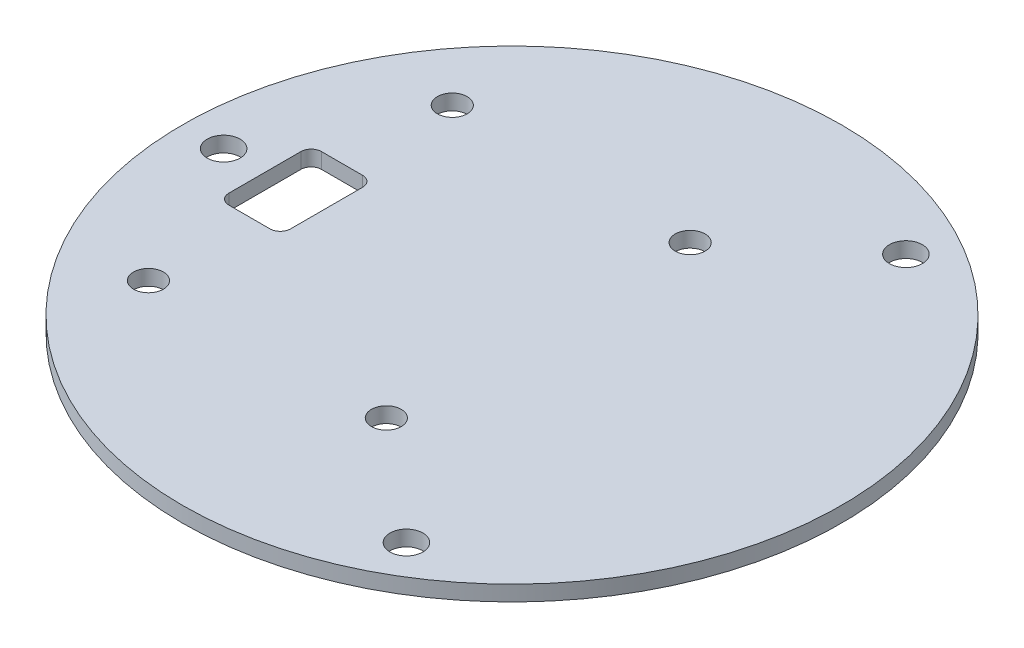
SolidWorks part; units mm, degrees
note: The reader was unsure of these and kept them because the rebuilt part matched: thickness of "Base-Flange1", "Sheet-Metal1", "Sheet-Metal2", "Sheet-Metal4", "Sheet-Metal5".
ref_plane "Front Plane" through (0, 0, 0) normal (0, 0, 1) x (1, 0, 0)
ref_plane "Top Plane" through (0, 0, 0) normal (0, 1, 0) x (1, 0, 0)
ref_plane "Right Plane" through (0, 0, 0) normal (1, 0, 0) x (0, 0, -1)
sketch "Sketch1" plane through (0, 0, 0) normal (0, 1, 0) x (1, 0, 0)
  circle A1 centre (0, 0) radius 32
  dimension "D2" = 64
base flange "Base-Flange1" sketch "Sketch1" thickness 1.5 reverse thickness direction no parameters "D1"=1.5
sketch "Sketch6" plane through (0, 0, 0) normal (0, 1, 0) x (1, 0, 0)
  line L0 (0, 0) -> (-28, 0) construction
  line L5 (0, 0) -> (14, 24.2487) construction
  line L7 (0, 0) -> (14, -24.2487) construction
  circle A5 centre (-28, 0) radius 1.6
  circle A6 centre (14, 24.2487) radius 1.6
  circle A7 centre (14, -24.2487) radius 1.6
  point P11 (0, 0)
  dimension "D1" = 28
  dimension "D2" = 3.2
  dimension "D3" = 3
extrude "Cut-Extrude1" cut sketch "Sketch6" against normal through all normal cut yes
sketch "Sketch7" plane through (0, 0, 0) normal (0, 1, 0) x (1, 0, 0)
  line L0 (-21, 4.5) -> (-21, -4.5) construction
  line L1 (-18, 4.5) -> (-24, 4.5)
  line L2 (-18, 4.5) -> (-18, -4.5)
  line L3 (-18, -4.5) -> (-24, -4.5)
  line L4 (-24, 4.5) -> (-24, -4.5)
  point P7 (-18, 0)
  dimension "D1" = 6
  dimension "D2" = 9
  dimension "D3" = 21
extrude "Cut-Extrude2" cut sketch "Sketch7" against normal through all normal cut yes
fillet "Fillet1" radius 1 4 edges at (-24, -0.75, 4.5) (-18, -0.75, 4.5) (-18, -0.75, -4.5) (-24, -0.75, -4.5)
sketch "Sketch8" plane through (0, -1.5, 0) normal (0, -1, 0) x (1, 0, 0)
  circle A0 centre (2.55, -14.75) radius 1.45 construction
  circle A1 centre (2.55, 14.75) radius 1.45 construction
  circle A2 centre (-20.55, 14.75) radius 1.45 construction
  circle A3 centre (-20.55, -14.75) radius 1.45 construction
  circle A4 centre (2.55, -14.75) radius 1.45
  circle A5 centre (2.55, 14.75) radius 1.45
  circle A6 centre (-20.55, 14.75) radius 1.45
  circle A7 centre (-20.55, -14.75) radius 1.45
extrude "Cut-Extrude3" cut sketch "Sketch8" against normal through all normal cut yes
sketch "Bend-Lines1" [suppressed] plane through (0, 0, 0) normal (0, 1, 0) x (1, 0, 0)
sketch "Bounding-Box1" [suppressed] plane through (0, 0, 0) normal (0, 1, 0) x (1, 0, 0)
sheet metal parameters "Sheet-Metal1" thickness 1.5 parameters "D1"=2, "D7"=2
flat pattern "Flat-Pattern1" [suppressed]
sketch "Bend-Lines2" plane through (0, 0, 0) normal (0, 1, 0) x (1, 0, 0)
sketch3d "Bounding-Box2" [suppressed]
  line L0 (32.05, -31.9499, 0) -> (-31.9499, -32.0499, 0) construction
  line L1 (31.95, 32.05, 0) -> (-32.0499, 31.95, 0) construction
  line L2 (32.05, -31.9499, 0) -> (31.95, 32.05, 0) construction
  line L3 (-31.9499, -32.0499, 0) -> (-32.0499, 31.95, 0) construction
sheet metal parameters "Sheet-Metal2" thickness 1.5 parameters "D1"=2, "D7"=2
flat pattern "Flat-Pattern1"
sketch "Bend-Lines2" plane through (0, 0, 0) normal (0, 1, 0) x (1, 0, 0)
sketch3d "Bounding-Box2" [suppressed]
  line L0 (32.05, -31.9499, 0) -> (-31.9499, -32.0499, 0) construction
  line L1 (31.95, 32.05, 0) -> (-32.0499, 31.95, 0) construction
  line L2 (32.05, -31.9499, 0) -> (31.95, 32.05, 0) construction
  line L3 (-31.9499, -32.0499, 0) -> (-32.0499, 31.95, 0) construction
sheet metal parameters "Sheet-Metal4" thickness 1.5 parameters "D1"=2, "D7"=2
flat pattern "Flat-Pattern1"
sketch "Bend-Lines2" plane through (0, 0, 0) normal (0, 1, 0) x (1, 0, 0)
sketch3d "Bounding-Box2" [suppressed]
  line L0 (32.05, -31.9499, 0) -> (-31.9499, -32.0499, 0) construction
  line L1 (31.95, 32.05, 0) -> (-32.0499, 31.95, 0) construction
  line L2 (32.05, -31.9499, 0) -> (31.95, 32.05, 0) construction
  line L3 (-31.9499, -32.0499, 0) -> (-32.0499, 31.95, 0) construction
sheet metal parameters "Sheet-Metal5" thickness 1.5 parameters "D1"=2, "D7"=2
flat pattern "Flat-Pattern1"
sketch "Bend-Lines2" plane through (0, 0, 0) normal (0, 1, 0) x (1, 0, 0)
sketch3d "Bounding-Box2" [suppressed]
  line L0 (32.05, -31.9499, 0) -> (-31.9499, -32.0499, 0) construction
  line L1 (31.95, 32.05, 0) -> (-32.0499, 31.95, 0) construction
  line L2 (32.05, -31.9499, 0) -> (31.95, 32.05, 0) construction
  line L3 (-31.9499, -32.0499, 0) -> (-32.0499, 31.95, 0) construction
